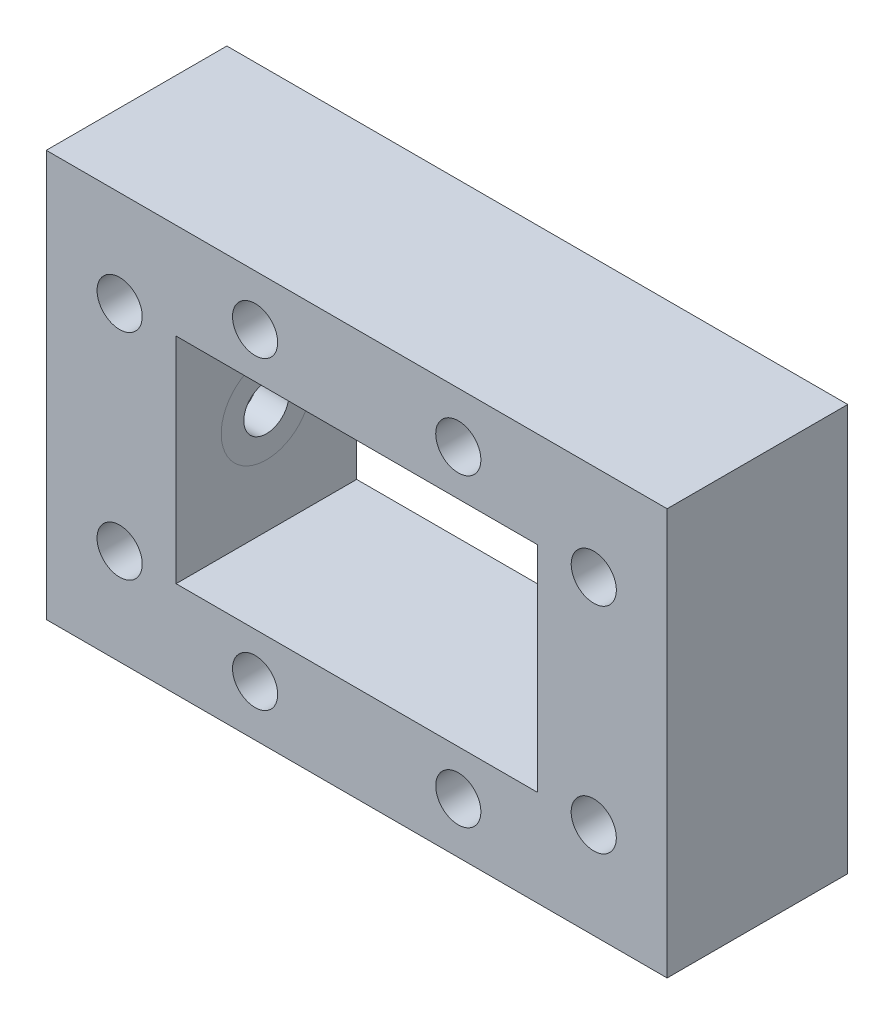
SolidWorks part; units mm, degrees
material "Alumina"
ref_plane "Front Plane" through (0, 0, 0) normal (0, 0, 1) x (1, 0, 0)
ref_plane "Top Plane" through (0, 0, 0) normal (0, 1, 0) x (1, 0, 0)
ref_plane "Right Plane" through (0, 0, 0) normal (1, 0, 0) x (0, 0, -1)
sketch "Sketch1" plane through (0, 0, 0) normal (0, 0, 1) x (1, 0, 0)
  line L0 (0, 0) -> (50000, 0) construction
  line L1 (-27.5, 18) -> (27.5, 18)
  line L2 (-27.5, 18) -> (-27.5, -18)
  line L3 (-27.5, -18) -> (27.5, -18)
  line L4 (27.5, 18) -> (27.5, -18)
  line L5 (-27.5, 18) -> (27.5, -18) construction
  line L6 (-27.5, -18) -> (27.5, 18) construction
  line L7 (0, 0) -> (0, 50000) construction
  line L9 (-16, 9.5) -> (16, 9.5)
  line L10 (-16, 9.5) -> (-16, -9.5)
  line L11 (-16, -9.5) -> (16, -9.5)
  line L12 (16, 9.5) -> (16, -9.5)
  line L13 (-16, 9.5) -> (16, -9.5) construction
  line L14 (-16, -9.5) -> (16, 9.5) construction
  circle A0 centre (-21, 9.5) radius 2
  circle A1 centre (-9, 13.5) radius 2
  circle A2 centre (-21, -9.5) radius 2
  circle A3 centre (-9, -13.5) radius 2
  circle A4 centre (9, -13.5) radius 2
  circle A5 centre (21, -9.5) radius 2
  circle A6 centre (9, 13.5) radius 2
  circle A7 centre (21, 9.5) radius 2
  point P0 (0, 0)
  point P10 (0, 0)
  dimension "D9" = 4
  dimension "D1" = 55
  dimension "D2" = 36
  dimension "D3" = 32
  dimension "D4" = 19
  dimension "D5" = 9.5
  dimension "D6" = 13.5
  dimension "D7" = 9
  dimension "D8" = 21
extrude "Boss-Extrude1" add sketch "Sketch1" along normal mid plane 16
sketch "Sketch2" plane through (0, -18, 0) normal (0, -1, 0) x (1, 0, 0)
  line L0 (0, 0) -> (0, 50000) construction
  line L1 (0, 0) -> (-50000, 0) construction
  circle A0 centre (-15, 0) radius 2
  circle A1 centre (15, 0) radius 2
  point P7 (0, 0)
  dimension "D2" = 4
  dimension "D1" = 30
extrude "Cut-Extrude1" cut sketch "Sketch2" against normal blind 7
cosmetic thread "Cosmetic Thread2" parameters "D2"=5
cosmetic thread "Cosmetic Thread3" parameters "D2"=5
sketch "Sketch3" plane through (-16, 0, 0) normal (1, 0, 0) x (0, 0, -1)
  circle A0 centre (0, 0) radius 2
  circle A1 centre (0, 0) radius 4
  dimension "D1" = 4
  dimension "D2" = 8
extrude "Cut-Extrude2" cut sketch "Sketch3" against normal through all contours A1 A0 | A0 region at (-16, 0, 0) region at (-16, 0, 3.8869)
extrude "Boss-Extrude2" add sketch "Sketch3<5>" against normal blind 4.5 separate body
sketch "Sketch3<5>" plane through (-16, 0, 0) normal (1, 0, 0) x (0, 0, -1) same geometry as "Sketch3"
sketch "Sketch4" plane through (0, 0, 0) normal (0, 0, 1) x (1, 0, 0)
  line L0 (0, 0) -> (-50000, 0) construction
  line L1 (-27.5, 0) -> (-27.5, 5)
  line L2 (-27.5, 4) -> (-27.5, -4) construction
  line L3 (-27.5, 18) -> (-27.5, -18) construction
  line L4 (-27.5, 5) -> (-20.5, 5)
  line L5 (-20.5, 5) -> (-17.6132, 0)
  line L6 (-17.6132, 0) -> (-27.5, 0)
  dimension "D1" = 60
  dimension "D2" = 10
  dimension "D3" = 7
revolve "Cut-Revolve1" cut sketch "Sketch4" angle 360 about L0
cosmetic thread "Cosmetic Thread1" parameters "D2"=12
